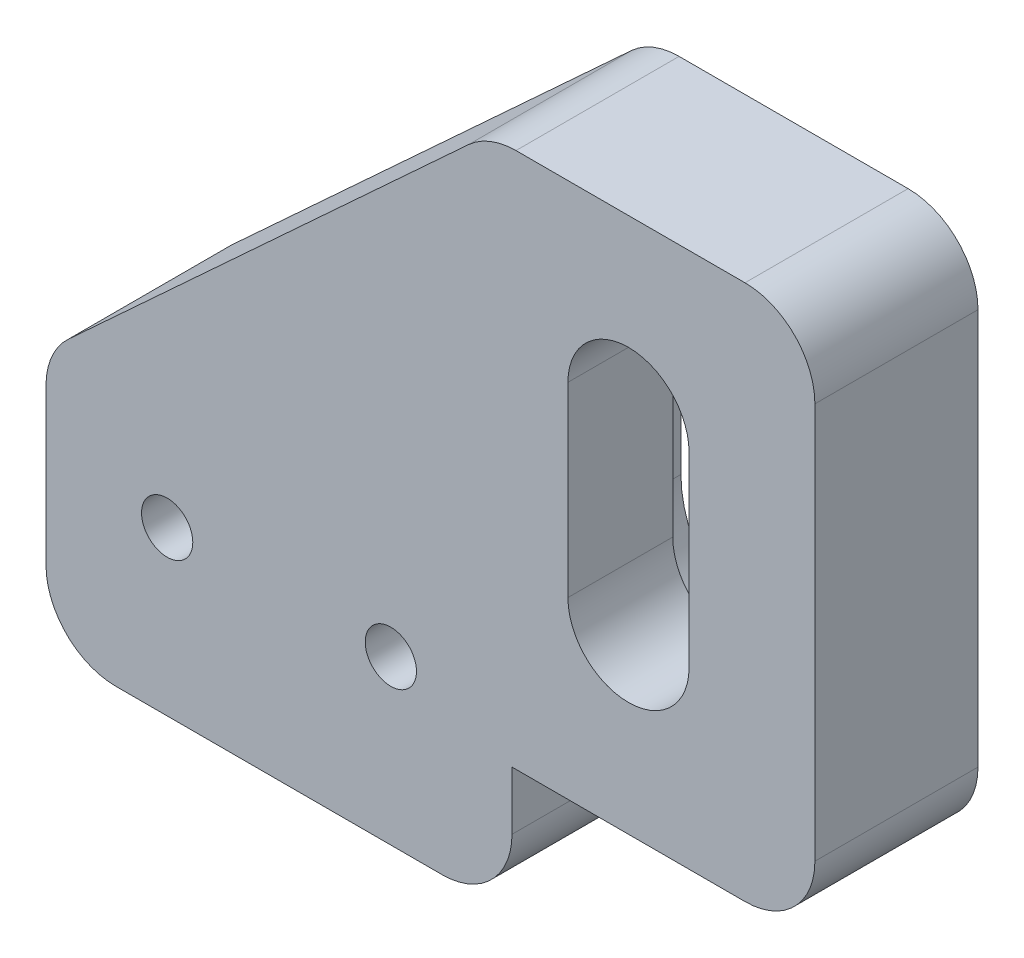
SolidWorks part; units mm, degrees
material "ABS"
ref_plane "Front Plane" through (0, 0, 0) normal (0, 0, 1) x (1, 0, 0)
ref_plane "Top Plane" through (0, 0, 0) normal (0, 1, 0) x (1, 0, 0)
ref_plane "Right Plane" through (0, 0, 0) normal (1, 0, 0) x (0, 0, -1)
sketch "Sketch1" plane through (0, 0, 0) normal (0, 0, 1) x (1, 0, 0)
  line L0 (3, 0) -> (17, 0)
  line L1 (20, 3) -> (20, 5.5)
  line L2 (20.1711, 28.5) -> (30, 28.5)
  line L3 (10, 0) -> (10, 20.2105) construction
  line L4 (25, 21) -> (25, 13) construction
  line L5 (0, 9.6846) -> (0, 3)
  line L6 (27.6, 21) -> (27.6, 13)
  line L7 (22.4, 21) -> (22.4, 13)
  line L8 (20, 5.5) -> (30, 5.5)
  line L9 (33, 8.5) -> (33, 25.5)
  line L10 (18.1386, 27.7066) -> (0.9676, 11.8912)
  line L11 (25, 5.5) -> (25, 28.5) construction
  arc A1 (30, 5.5) -> (33, 8.5) centre (30, 8.5) ccw
  circle A2 centre (5.2, 7) radius 1.1
  circle A3 centre (14.8, 7) radius 1.1
  arc A4 (27.6, 21) -> (22.4, 21) centre (25, 21) ccw
  arc A5 (22.4, 13) -> (27.6, 13) centre (25, 13) ccw
  arc A6 (33, 25.5) -> (30, 28.5) centre (30, 25.5) ccw
  arc A7 (20.1711, 28.5) -> (18.1386, 27.7066) centre (20.1711, 25.5) ccw
  arc A8 (0, 3) -> (3, 0) centre (3, 3) ccw
  arc A9 (17, 0) -> (20, 3) centre (17, 3) ccw
  arc A10 (0.9676, 11.8912) -> (0, 9.6846) centre (3, 9.6846) ccw
  point P7 (0, 28.6)
  point P14 (25, 17)
  point P32 (0, 28.6)
  point P35 (0, 0)
  point P38 (20, 0)
  point P40 (19, 28.5)
  point P43 (0, 11)
  dimension "D5" = 2.6
  dimension "D6" = 7.5
  dimension "D7" = 10
  dimension "D8" = 8
  dimension "D10" = 2.2
  dimension "D11" = 2.2
  dimension "D12" = 7
  dimension "D13" = 9.6
  dimension "D14" = 3
  dimension "D15" = 7.5
  dimension "D18" = 3
  dimension "D19" = 3
  dimension "D4" = 8
  dimension "D2" = 20
  dimension "D9" = 15
  dimension "D16" = 11
  dimension "D17" = 14
extrude "Boss-Extrude1" add sketch "Sketch1" along normal blind 7
ref_axis "Axis1" through (25, 21, 7) along (0, 0, -1)
ref_axis "Axis2" through (25, 13, 7) along (0, 0, -1)
sketch3d "3DSketch1"
  line L0 (25, 21, 0) -> (25, 13, 0) construction
  line L1 (25, 21, 7) -> (25, 21, 0) construction
  line L2 (25, 21, 7) -> (25, 21, 0) construction
  line L3 (25, 13, 7) -> (25, 13, 0) construction
  line L4 (25, 13, 7) -> (25, 13, 0) construction
  point P10 (25, 17, 0)
sketch "Sketch2" plane through (0, 0, 0) normal (0, 0, -1) x (-1, 0, 0)
  line L0 (-25, 21) -> (-25, 13) construction
  line L1 (-20.25, 21) -> (-20.25, 13)
  line L2 (-29.75, 21) -> (-29.75, 13)
  arc A0 (-20.25, 21) -> (-29.75, 21) centre (-25, 21) ccw
  arc A1 (-29.75, 13) -> (-20.25, 13) centre (-25, 13) ccw
  point P4 (-25, 17)
  dimension "D1" = 4.75
extrude "Cut-Extrude1" cut sketch "Sketch2" against normal blind 2.5
